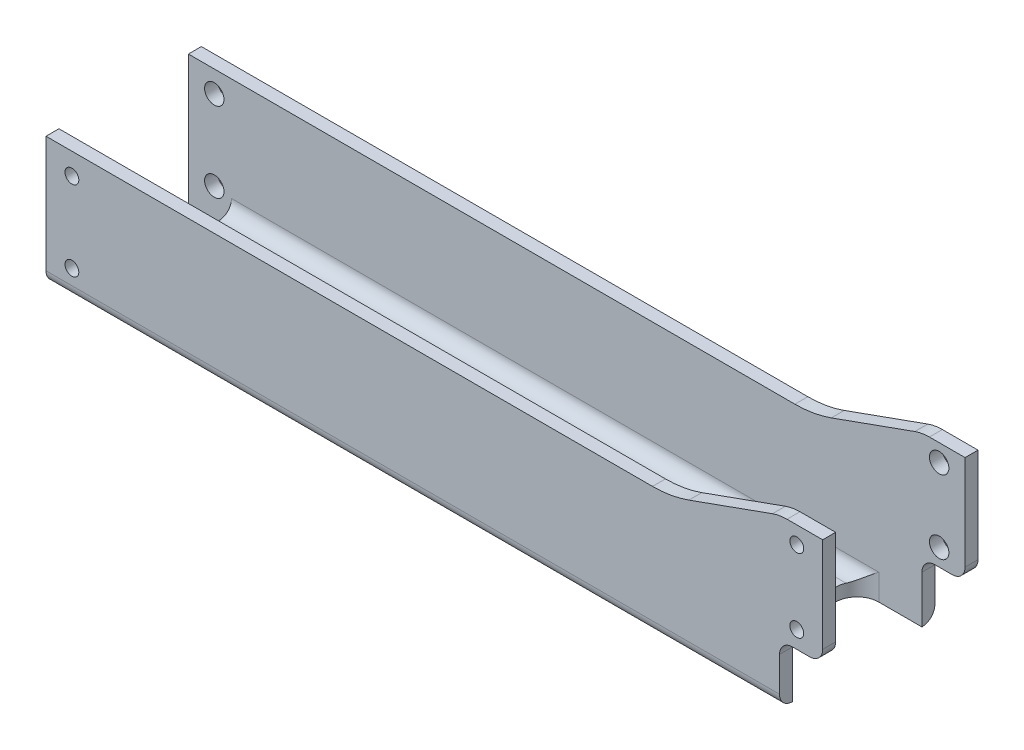
SolidWorks part; units mm, degrees
ref_plane "Front Plane" through (0, 0, 0) normal (0, 0, 1) x (1, 0, 0)
ref_plane "Top Plane" through (0, 0, 0) normal (0, 1, 0) x (1, 0, 0)
ref_plane "Right Plane" through (0, 0, 0) normal (1, 0, 0) x (0, 0, -1)
sketch "Sketch1" plane through (0, 0, 0) normal (0, 0, 1) x (1, 0, 0)
  line L0 (52.7874, 245.1803) -> (193.3525, 245.1803)
  line L4 (52.7874, 245.1803) -> (52.7874, 215.1803)
  line L5 (52.7874, 215.1803) -> (222.7874, 215.1803)
  line L6 (222.7874, 245.1803) -> (222.7874, 215.1803) construction
  line L7 (222.7874, 215.1803) -> (222.7874, 254.1811)
  line L8 (222.7874, 254.1811) -> (201.7956, 246.6492)
  line L9 (241.0832, 254.1811) -> (222.7874, 254.1811) construction
  arc A0 (201.7956, 246.6492) -> (193.3525, 245.1803) centre (193.3525, 270.1803) cw
extrude "Boss-Extrude1" add sketch "Sketch1" against normal blind 3
sketch "Sketch3" plane through (0, 0, -36) normal (0, 0, -1) x (-1, 0, 0)
  line L4 (-222.7874, 254.1811) -> (-222.7874, 215.1803)
  line L5 (-222.7874, 254.1811) -> (-222.7874, 215.1803)
  line L6 (-52.7874, 215.1803) -> (-52.7874, 245.1803)
  line L7 (-52.7874, 245.1803) -> (-193.3525, 245.1803)
  line L9 (-201.7956, 246.6492) -> (-222.7874, 254.1811)
  line L10 (-201.7956, 246.6492) -> (-222.7874, 254.1811)
  line L11 (-222.7874, 215.1803) -> (-52.7874, 215.1803)
  line L12 (-52.7874, 215.1803) -> (-52.7874, 245.1803)
  line L13 (-52.7874, 245.1803) -> (-193.3525, 245.1803)
  line L17 (-222.7874, 215.1803) -> (-52.7874, 215.1803)
  arc A1 (-201.7956, 246.6492) -> (-193.3525, 245.1803) centre (-193.3525, 270.1803) ccw
  arc A2 (-201.7956, 246.6492) -> (-193.3525, 245.1803) centre (-193.3525, 270.1803) ccw
  dimension "D1" = 0
extrude "Boss-Extrude2" add sketch "Sketch3" against normal blind 3 separate body
sketch "Sketch4" plane through (0, 0, -3) normal (0, 0, -1) x (-1, 0, 0)
  line L1 (-52.7874, 215.1803) -> (-207.7874, 215.1803)
  line L2 (-52.7874, 215.1803) -> (-52.7874, 218.1803)
  line L3 (-52.7874, 218.1803) -> (-207.7874, 218.1803)
  line L4 (-207.7874, 215.1803) -> (-207.7874, 218.1803)
extrude "Boss-Extrude3" add sketch "Sketch4" along normal up to surface (30 mm away) up to face at (157.7268, 236.8645, -33)
fillet "Fillet1" radius 5 2 edges at (207.7874, 216.6803, -33) (207.7874, 216.6803, -3)
ref_plane "Plane1" through (130.2874, 0, 0) normal (1, 0, 0) x (0, 0, -1)
fillet "Fillet2" radius 3 4 edges at (132.7874, 218.1803, -3) (132.7874, 218.1803, -33) (137.7874, 215.1803, 0) (137.7874, 215.1803, -36)
sketch "Sketch5" plane through (0, 218.1803, 0) normal (0, 1, 0) x (1, 0, 0)
  line L0 (52.7874, 33) -> (193.3525, 33) construction
  line L1 (52.7874, 3) -> (62.7874, 3)
  line L2 (52.7874, 3) -> (52.7874, 33)
  line L3 (52.7874, 33) -> (62.7874, 33)
  line L4 (62.7874, 3) -> (62.7874, 33)
extrude "Cut-Extrude1" cut sketch "Sketch5" against normal through all both and the other way through all
sketch "Sketch6" plane through (0, 0, 0) normal (0, 0, 1) x (1, 0, 0)
  line L0 (62.7877, 245.1806) -> (62.7877, 215.1806) construction
  line L1 (54.7876, 222.1805) -> (54.7876, 245.1805) construction
  line L2 (62.7877, 245.1806) -> (62.7877, 215.1806) construction
  line L3 (54.7876, 222.1805) -> (54.7876, 245.1805) construction
  line L4 (54.7876, 245.1805) -> (62.7877, 245.1806) construction
  line L5 (58.7876, 245.1805) -> (58.7876, 215.1803) construction
  line L6 (52.7874, 215.1803) -> (62.7874, 215.1803) construction
  circle A0 centre (58.7876, 240.1805) radius 1.6
  circle A1 centre (58.7876, 221.6803) radius 1.6
extrude "Cut-Extrude2" cut sketch "Sketch6" against normal blind 4
sketch "Sketch7" plane through (222.7874, 0, 0) normal (1, 0, 0) x (0, 0, -1)
  line L0 (0, 218.1803) -> (0, 254.1811) construction
  line L1 (3, 254.1811) -> (0, 254.1811)
  line L2 (3, 254.1811) -> (3, 229.1811)
  line L3 (3, 229.1811) -> (0, 229.1811)
  line L4 (0, 254.1811) -> (0, 229.1811)
  line L5 (36, 254.1811) -> (36, 218.1803) construction
  line L6 (33, 254.1811) -> (36, 254.1811)
  line L7 (33, 254.1811) -> (33, 229.1811)
  line L8 (33, 229.1811) -> (36, 229.1811)
  line L9 (36, 254.1811) -> (36, 229.1811)
extrude "Boss-Extrude4" add sketch "Sketch7" along normal blind 10
fillet "Fillet3" radius 3 4 edges at (222.7874, 229.1811, -34.5) (222.7874, 229.1811, -1.5) (232.7874, 229.1811, -34.5) (232.7874, 229.1811, -1.5)
sketch "Sketch9" plane through (0, 0, 0) normal (0, 0, 1) x (1, 0, 0)
  line L0 (230.7874, 254.1811) -> (230.7874, 229.3173) construction
  line L1 (230.7874, 254.1811) -> (230.7874, 229.3173) construction
  line L2 (222.7874, 226.1811) -> (222.7874, 254.1811) construction
  line L3 (222.7874, 226.1811) -> (222.7874, 254.1811) construction
  line L4 (222.7874, 254.1811) -> (230.7874, 254.1811) construction
  line L5 (226.7874, 254.1811) -> (226.7874, 229.1811) construction
  circle A0 centre (226.7874, 250.1811) radius 1.6
  circle A1 centre (226.7874, 233.1811) radius 1.6
extrude "Cut-Extrude3" cut sketch "Sketch9" against normal blind 5
sketch "Sketch10" plane through (0, 0, -36) normal (0, 0, -1) x (-1, 0, 0)
  circle A0 centre (-226.7874, 250.1811) radius 2.25
  circle A1 centre (-226.7874, 233.1811) radius 2.25
  circle A2 centre (-58.7876, 240.1805) radius 2.25
  circle A3 centre (-58.7876, 221.6803) radius 2.25
extrude "Cut-Extrude4" cut sketch "Sketch10" against normal blind 3
fillet "Fillet4" radius 10 2 edges at (222.7874, 254.1811, -34.5) (222.7874, 254.1811, -1.5)
